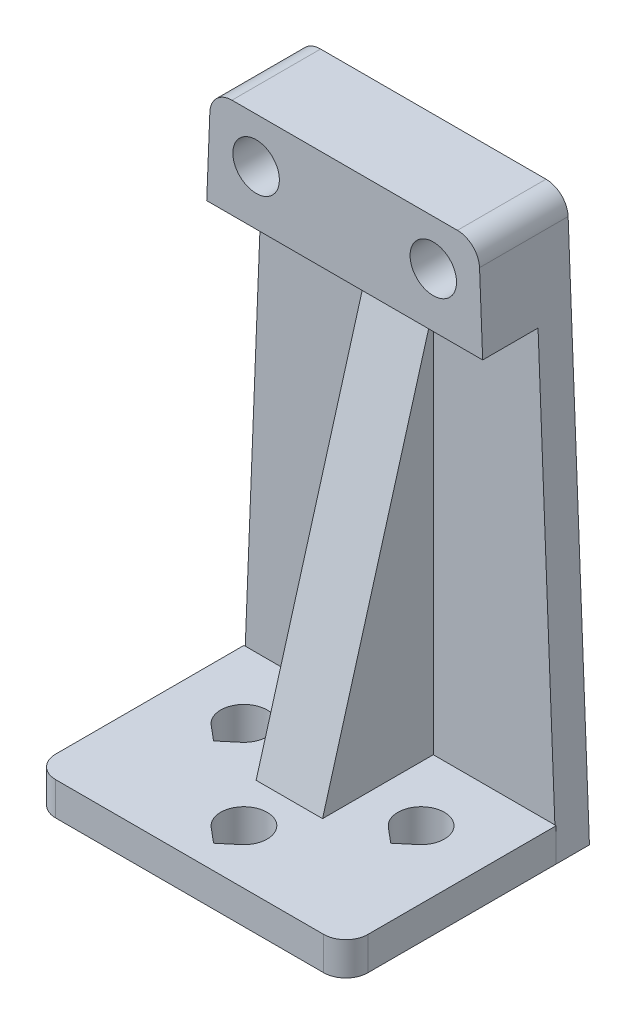
SolidWorks part; units mm, degrees
ref_plane "Front Plane" through (0, 0, 0) normal (0, 0, 1) x (1, 0, 0)
ref_plane "Top Plane" through (0, 0, 0) normal (0, 1, 0) x (1, 0, 0)
ref_plane "Right Plane" through (0, 0, 0) normal (1, 0, 0) x (0, 0, -1)
sketch "Sketch1" plane through (0, 0, 0) normal (0, 1, 0) x (1, 0, 0)
  line L0 (-8, -6.1) -> (8, -6.1) construction
  line L1 (-14.1, -19) -> (14.1, -19)
  line L2 (-14.1, -19) -> (-14.1, 0)
  line L3 (-14.1, 0) -> (14.1, 0)
  line L4 (14.1, -19) -> (14.1, 0)
  line L5 (-9.3499, -7.7087) -> (-8, -8.8414)
  line L6 (-8, -8.8414) -> (-6.6501, -7.7087)
  line L7 (-1.3499, -15.7087) -> (0, -16.8414)
  line L8 (0, -16.8414) -> (1.3499, -15.7087)
  line L9 (6.6501, -7.7087) -> (8, -8.8414)
  line L10 (8, -8.8414) -> (9.3499, -7.7087)
  arc A0 (-6.6501, -7.7087) -> (-9.3499, -7.7087) centre (-8, -6.1) ccw
  arc A1 (9.3499, -7.7087) -> (6.6501, -7.7087) centre (8, -6.1) ccw
  arc A2 (1.3499, -15.7087) -> (-1.3499, -15.7087) centre (0, -14.1) ccw
  point P4 (0, 0)
  point P10 (0, -6.1)
  dimension "D3" = 4.2
  dimension "D1" = 28.2
  dimension "D2" = 19
  dimension "D4" = 16
  dimension "D5" = 4
  dimension "D6" = 8
  dimension "D7" = 100
  dimension "D8" = 100
  dimension "D9" = 100
extrude "Boss-Extrude1" add sketch "Sketch1" along normal blind 3
sketch "Sketch2" plane through (0, 0, 0) normal (0, 0, -1) x (-1, 0, 0)
  line L0 (-8, 46) -> (8, 46) construction
  line L1 (-14.1, 0) -> (14.1, 0)
  line L2 (-14.1, 0) -> (-12.1, 50.1)
  line L3 (-12.1, 50.1) -> (12.1, 50.1)
  line L4 (14.1, 0) -> (12.1, 50.1)
  circle A0 centre (-8, 46) radius 2.1
  circle A1 centre (8, 46) radius 2.1
  point P5 (0, 46)
  point P12 (0, 50.1)
  dimension "D1" = 4.2
  dimension "D2" = 16
  dimension "D3" = 2
  dimension "D4" = 2
  dimension "D5" = 46
extrude "Boss-Extrude2" add sketch "Sketch2" along normal blind 3
sketch "Sketch3" plane through (0, 0, 0) normal (1, 0, 0) x (0, 0, -1)
  line L0 (0, 3) -> (-10, 3)
  line L1 (-19, 3) -> (0, 3) construction
  line L2 (-10, 3) -> (0, 38)
  line L3 (0, 50.1) -> (0, 3) construction
  line L4 (0, 38) -> (0, 3)
  dimension "D1" = 10
  dimension "D2" = 35
extrude "Boss-Extrude3" add sketch "Sketch3" along normal mid plane 6
fillet "Fillet1" radius 2 4 edges at (12.1, 50.1, -1.5) (-12.1, 50.1, -1.5) (14.1, 1.5, 19) (-14.1, 1.5, 19)
sketch "Sketch4" plane through (0, 0, 0) normal (0, 0, 1) x (1, 0, 0)
  line L0 (-10.1782, 50.1) -> (10.1782, 50.1) construction
  line L1 (-10.1782, 50.1) -> (10.1782, 50.1)
  line L2 (-12.1767, 48.1798) -> (-12.4593, 41.1)
  line L3 (-13.9802, 3) -> (-12.1767, 48.1798) construction
  line L4 (-12.4593, 41.1) -> (12.4593, 41.1)
  line L5 (12.1767, 48.1798) -> (13.9802, 3) construction
  line L6 (12.4593, 41.1) -> (12.1767, 48.1798)
  circle A0 centre (-8, 46) radius 2.1 construction
  circle A1 centre (8, 46) radius 2.1 construction
  arc A2 (12.1767, 48.1798) -> (10.1782, 50.1) centre (10.1782, 48.1) ccw construction
  arc A3 (-10.1782, 50.1) -> (-12.1767, 48.1798) centre (-10.1782, 48.1) ccw construction
  circle A4 centre (-8, 46) radius 2.1
  circle A5 centre (8, 46) radius 2.1
  arc A6 (12.1767, 48.1798) -> (10.1782, 50.1) centre (10.1782, 48.1) ccw
  arc A7 (-10.1782, 50.1) -> (-12.1767, 48.1798) centre (-10.1782, 48.1) ccw
  dimension "D1" = 9
extrude "Boss-Extrude4" add sketch "Sketch4" along normal blind 5
equation "\"width\"= 24"
equation "\"thk\"= 3"
equation "\"holesize\"= 4.2"
equation "\"holedistance\"= ( 20 + 12 ) / 2"
equation "\"threaded_hole\"= 3.9"
equation "\"fillet_radius\"= 2"
equation "\"ground_clearance\"= 25"
equation "\"tire_thk\"= 3"
equation "\"innerwheel_diam\" = \"wheel_diam\"-2*\"tire_thk\""
equation "\"innerwheel_thk\"= 8"
equation "\"wheel_diam\"= 2*(\"width\"/2+\"ground_clearance\")"
equation "\"coloursensor_holesize\"= 2.65"
equation "\"hole_to_edge\" = 4"
equation "\"D1@Sketch1\"=\"holedistance\"+ \"holesize\" + 2 * \"hole_to_edge\""
equation "\"D3@Sketch1\"=\"holesize\""
equation "\"D4@Sketch1\"=\"holedistance\""
equation "\"D6@Sketch1\"=\"holedistance\"/2"
equation "\"D5@Sketch1\"=\"hole_to_edge\""
equation "\"D1@Boss-Extrude1\"=\"thk\""
equation "\"D1@Sketch2\"=\"holesize\""
equation "\"D2@Sketch2\"=\"holedistance\""
equation "\"D4@Sketch2\"=\"D3@Sketch2\""
equation "\"D1@Boss-Extrude2\"=\"thk\""
equation "\"D1@Fillet1\"=\"fillet_radius\""
equation "\"D8@Sketch1\"=\"D7@Sketch1\""
equation "\"D9@Sketch1\"=\"D7@Sketch1\""
equation "\"D5@Sketch2\"=42 + \"thk\" + 1"
